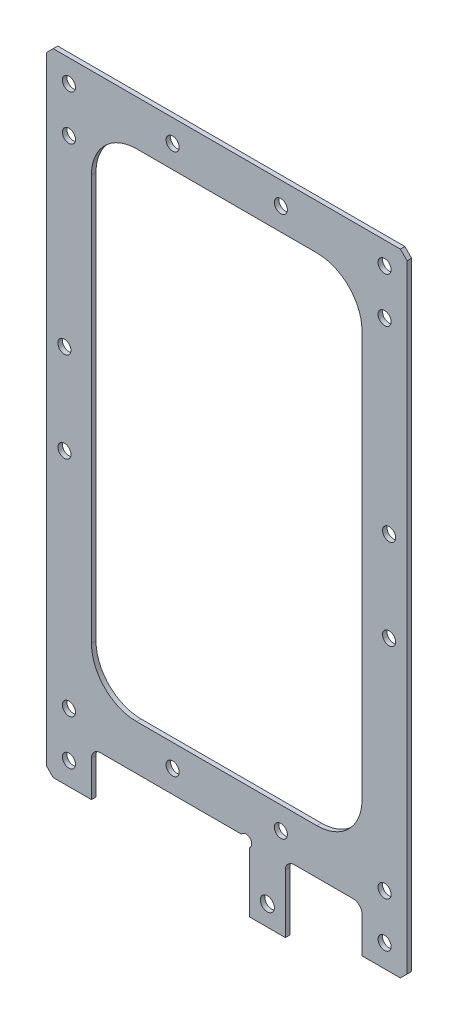
SolidWorks part; units mm, degrees
material "Hexcel AS4C (3000 Filaments)"
ref_plane "Front Plane" through (0, 0, 0) normal (0, 0, 1) x (1, 0, 0)
ref_plane "Top Plane" through (0, 0, 0) normal (0, 1, 0) x (1, 0, 0)
ref_plane "Right Plane" through (0, 0, 0) normal (1, 0, 0) x (0, 0, -1)
sketch "Sketch87" plane through (0, 0, 0) normal (0, 0, 1) x (1, 0, 0)
  line L0 (-40, 70) -> (-40, -70)
  line L1 (-40, -70) -> (-30, -70)
  line L2 (-30, -70) -> (-30, -60)
  line L3 (-30, -60) -> (30, -60)
  line L4 (30, -60) -> (30, -70)
  line L5 (30, -70) -> (40, -70)
  line L6 (40, -70) -> (40, 70)
  line L7 (40, 70) -> (-40, 70)
  line L8 (0, 0) -> (0, 80.6058) construction
  line L9 (0, 0) -> (66.198, 0) construction
  dimension "D1" = 80
  dimension "D2" = 10
  dimension "D3" = 10
  dimension "D4" = 70
  dimension "D5" = 140
extrude "Boss-Extrude12" add sketch "Sketch87" along normal blind 1
sketch "Sketch88" plane through (0, 0, 1) normal (0, 0, 1) x (1, 0, 0)
  line L0 (0, 0) -> (0, 76.795) construction
  line L1 (-30, -50) -> (30, -50)
  line L2 (-30, -50) -> (-30, 60)
  line L3 (-30, 60) -> (30, 60)
  line L4 (30, -50) -> (30, 60)
  line L5 (-40, 70) -> (-40, -70) construction
  line L6 (40, 70) -> (-40, 70) construction
  line L7 (-30, -60) -> (30, -60) construction
  dimension "D1" = 10
  dimension "D2" = 10
  dimension "D3" = 10
extrude "Cut-Extrude1" cut sketch "Sketch88" against normal blind 1
fillet "Fillet1" radius 10 4 edges at (-30, -50, 0.5) (30, -50, 0.5) (30, 60, 0.5) (-30, 60, 0.5)
hole_wizard "M2.5 Clearance Hole1" positions "Sketch90" profile "Sketch89" hole size "M2.5" standard "DIN"
sketch "Sketch90" plane through (0, 0, 0) normal (0, 0, -1) x (-1, 0, 0)
  line L0 (0, 0) -> (0, -74.8489) construction
  line L2 (-40, 5) -> (68.9893, 5) construction
  line L3 (-40, -70) -> (-40, 70) construction
  line L5 (-40, 70) -> (40, 70) construction
  line L6 (30, -60) -> (-30, -60) construction
  point P0 (35, -65)
  point P1 (35, -55)
  point P12 (-35, -55)
  point P15 (-35, -65)
  point P19 (12, -55)
  point P29 (-12, -55)
  point P41 (-12, 65)
  point P42 (12, 65)
  point P43 (-35, 65)
  point P44 (35, 65)
  point P45 (-35, 55)
  point P47 (35, 55)
  dimension "D1" = 23
  dimension "D2" = 10
sketch "Sketch89" plane through (-35, -65, 0) normal (1, 0, 0) x (0, 1, 0)
  line L0 (0, 0) -> (0, 11.5)
  line L1 (0, 11.5) -> (1.45, 11.5)
  line L2 (1.45, 11.5) -> (1.45, 0)
  line L5 (1.45, 0) -> (0, 0)
  line L10 (0, 11.5) -> (-1.45, 11.5) construction
  line L11 (0, -6.35) -> (0, 107.95) construction
  dimension "Hole Dia." = 2.9
  dimension "Hole Depth" = 11.5
  dimension "Drill Angle" = 180
sketch "Sketch91" plane through (0, 0, 0) normal (0, 0, -1) x (-1, 0, 0)
  line L0 (-40, -70) -> (-40, 70) construction
  line L1 (-13, -60) -> (-5, -60)
  line L2 (-13, -60) -> (-13, -75)
  line L3 (-13, -75) -> (-5, -75)
  line L4 (-5, -60) -> (-5, -75)
  line L5 (-30, -70) -> (-40, -70) construction
  line L6 (30, -60) -> (-30, -60) construction
  circle A0 centre (-9, -70.5) radius 1.55
  dimension "D4" = 3.1
  dimension "D5" = 31
  dimension "D6" = 0.5
  dimension "D1" = 27
  dimension "D2" = 8
  dimension "D3" = 5
extrude "Boss-Extrude13" add sketch "Sketch91" against normal up to surface (1 mm away) up to face at (-33.55, -65, 1)
fillet "Fillet2" radius 2 3 edges at (30, -60, 0.5) (-30, -60, 0.5) (13, -60, 0.5)
chamfer "Chamfer1" distance 1.5 angle 45 4 edges at (40, 70, 0.5) (-40, 70, 0.5) (-40, -70, 0.5) (40, -70, 0.5)
sketch "Sketch93" plane through (0, 0, 0) normal (0, 0, -1) x (-1, 0, 0)
  line L0 (-5, -60) -> (-4.2929, -60.7071) construction
  line L1 (28, -60) -> (-5, -60) construction
  line L2 (-5, -75) -> (-5, -60) construction
  circle A0 centre (-4.2929, -60.7071) radius 1.25
  dimension "D1" = 2.5
  dimension "D2" = 1
extrude "Cut-Extrude2" cut sketch "Sketch93" against normal blind 10
hole_wizard "M2.5 Clearance Hole2" positions "Sketch95" profile "Sketch94" hole size "M2.5" standard "DIN"
sketch "Sketch95" plane through (0, 0, 0) normal (0, 0, -1) x (-1, 0, 0)
  line L0 (-40, -68.5) -> (-40, 68.5) construction
  line L1 (-38.5, 70) -> (38.5, 70) construction
  point P0 (-36, 14)
  point P6 (-36, -6)
  dimension "D1" = 4
  dimension "D2" = 56
  dimension "D3" = 76
sketch "Sketch94" plane through (36, 14, 0) normal (1, 0, 0) x (0, 1, 0)
  line L0 (0, 0) -> (0, 30)
  line L1 (0, 30) -> (1.45, 30)
  line L2 (1.45, 30) -> (1.45, 0)
  line L5 (1.45, 0) -> (0, 0)
  line L10 (0, 30) -> (-1.45, 30) construction
  line L11 (0, -6.35) -> (0, 107.95) construction
  dimension "Hole Dia." = 2.9
  dimension "Hole Depth" = 30
  dimension "Drill Angle" = 180
mirror "Mirror1" about plane through (0, 0, 0) normal (1, 0, 0) of "M2.5 Clearance Hole2"
